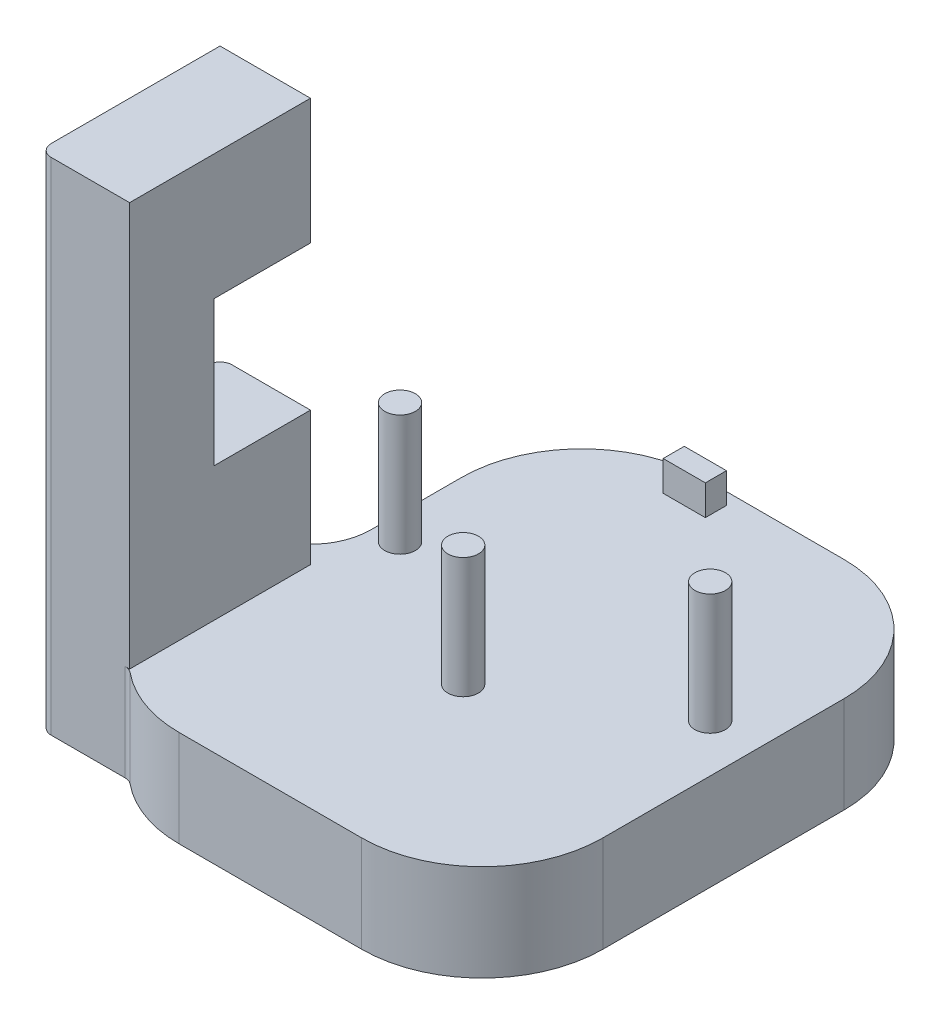
SolidWorks part; units mm, degrees
ref_plane "Front Plane" through (0, 0, 0) normal (0, 0, 1) x (1, 0, 0)
ref_plane "Top Plane" through (0, 0, 0) normal (0, 1, 0) x (1, 0, 0)
ref_plane "Right Plane" through (0, 0, 0) normal (1, 0, 0) x (0, 0, -1)
sketch "Sketch5" plane through (0, 0, 0) normal (0, 1, 0) x (1, 0, 0)
  line L1 (31.75, 40) -> (-31.75, 40)
  line L2 (31.75, 40) -> (31.75, -40)
  line L3 (31.75, -40) -> (-31.75, -40)
  line L4 (-31.75, 40) -> (-31.75, -40)
  line L5 (31.75, 40) -> (-31.75, -40) construction
  line L6 (31.75, -40) -> (-31.75, 40) construction
  point P0 (0, 0)
  dimension "D1" = 80
  dimension "D2" = 63.5
extrude "Boss-Extrude4" add sketch "Sketch5" along normal blind 16
sketch "Sketch6" plane through (0, 16, 0) normal (0, 1, 0) x (1, 0, 0)
  line L0 (31.75, 40) -> (-31.75, 40) construction
  line L1 (-5.75, 38) -> (-12.75, 38)
  line L2 (-5.75, 38) -> (-5.75, 34.5)
  line L3 (-5.75, 34.5) -> (-12.75, 34.5)
  line L4 (-12.75, 38) -> (-12.75, 34.5)
  line L5 (-5.75, 38) -> (-12.75, 34.5) construction
  line L6 (-5.75, 34.5) -> (-12.75, 38) construction
  line L9 (0, 0) -> (0, 40) construction
  line L10 (-31.75, 40) -> (-31.75, -40) construction
  point P0 (-9.25, 36.25)
  dimension "D1" = 7
  dimension "D2" = 3.5
  dimension "D3" = 2
  dimension "D4" = 19
extrude "Boss-Extrude5" add sketch "Sketch6" along normal blind 5 contours L3 L4 L1 L2
sketch "Sketch9" plane through (0, 0, 0) normal (0, 1, 0) x (1, 0, 0)
  line L0 (-31.75, 40) -> (-31.75, -40) construction
  line L5 (-31.75, -35) -> (-46.75, -35)
  line L6 (-31.75, -35) -> (-31.75, -5)
  line L7 (-31.75, -5) -> (-46.75, -5)
  line L8 (-46.75, -35) -> (-46.75, -5)
  line L9 (-31.75, -40) -> (31.75, -40) construction
  point P13 (-39.25, -5)
  dimension "D4" = 5
  dimension "D5" = 30
  dimension "D6" = 7.5
sketch "Sketch13" plane through (0, 16, 0) normal (0, 1, 0) x (1, 0, 0)
  line L0 (-31.75, 40) -> (-31.75, -40) construction
  line L2 (-31.75, -40) -> (31.75, -40) construction
  circle A0 centre (-27.6098, 5.72) radius 2.54
  circle A1 centre (23.8252, 5.72) radius 2.54
  circle A2 centre (-1.905, -9.52) radius 2.54
  dimension "D1" = 4.1402
  dimension "D3" = 5.08
  dimension "D4" = 51.435
  dimension "D6" = 5.08
  dimension "D7" = 5.08
  dimension "D2" = 45.72
  dimension "D5" = 45.72
  dimension "D8" = 25.7048
  dimension "D9" = 15.24
extrude "Boss-Extrude8" add sketch "Sketch13" along normal blind 20
extrude "Boss-Extrude10" add sketch "Sketch9" along normal blind 83 contours L8 L7 L6 L5
sketch "Sketch14" plane through (0, 0, 5) normal (0, 0, -1) x (-1, 0, 0)
  line L0 (31.75, 83) -> (31.75, 16) construction
  line L1 (31.75, 38.2) -> (46.75, 38.2)
  line L2 (31.75, 38.2) -> (31.75, 62.2)
  line L3 (31.75, 62.2) -> (46.75, 62.2)
  line L4 (46.75, 38.2) -> (46.75, 62.2)
  line L5 (46.75, 83) -> (46.75, 0) construction
  line L6 (31.75, 83) -> (46.75, 83) construction
  dimension "D1" = 20.8
  dimension "D2" = 24
extrude "Cut-Extrude1" cut sketch "Sketch14" against normal blind 16 contours L3 L4 L1 L2
fillet "Fillet1" radius 20 4 edges at (-31.75, 8, -40) (31.75, 8, -40) (-31.75, 8, 40) (31.75, 8, 40)
fillet "Fillet2" radius 10 1 edges at (-31.75, 8, 5)
fillet "Fillet3" radius 2 3 edges at (-31.75, 8, 35) (-46.75, 41.5, 35) (-46.75, 19.1, 5)
